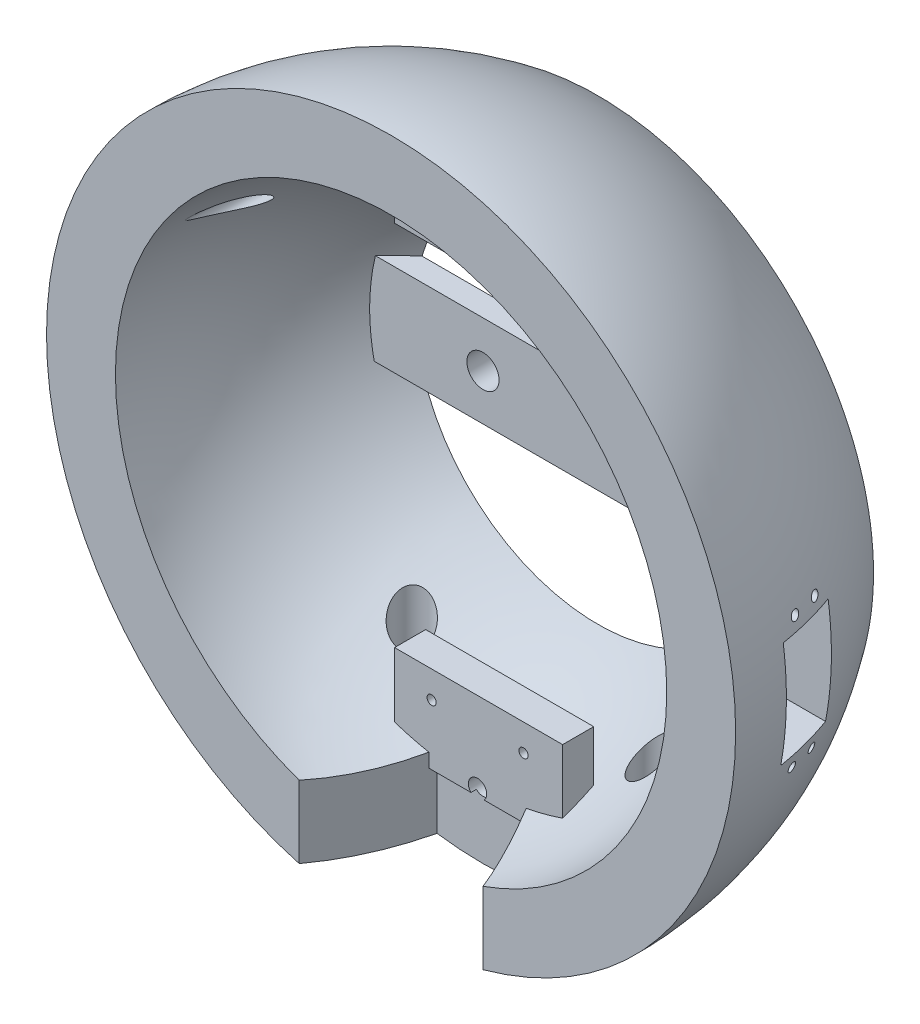
SolidWorks part; units mm, degrees
material "ABS"
ref_plane "Plano frontal" through (0, 0, 0) normal (0, 0, 1) x (1, 0, 0)
ref_plane "Plano superior" through (0, 0, 0) normal (0, 1, 0) x (1, 0, 0)
ref_plane "Plano direito" through (0, 0, 0) normal (1, 0, 0) x (0, 0, -1)
sketch "Esboço1" plane through (0, 0, 0) normal (0, 0, 1) x (1, 0, 0)
  line L0 (-60, 0) -> (-75, 0)
  line L1 (-60, 0) -> (-211.1575, 0) construction
  line L2 (75, 0) -> (60, 0)
  arc A0 (60, 0) -> (-60, 0) centre (0, 0) ccw
  arc A1 (75, 0) -> (-75, 0) centre (0, 0) ccw
  dimension "D1" = 120
  dimension "D2" = 150
revolve "Revolução1" add sketch "Esboço1" angle 180 about L1
ref_axis "Eixo1" through (0, 0, -79.24) along (0, 0, 1)
sketch "Esboço5" plane through (0, 0, 0) normal (0, 1, 0) x (1, 0, 0)
  line L0 (-75, 0) -> (75, 0) construction
  circle A0 centre (26, 30.5) radius 3.95
  circle A1 centre (-26, 30.5) radius 3.95
  dimension "D1" = 7.9
  dimension "D2" = 7.9
  dimension "D6" = 26
  dimension "D3" = 26
  dimension "D4" = 30.5
  dimension "D5" = 30.5
extrude "Corte-extrusão2" cut sketch "Esboço5" against normal through all
sketch "Esboço6" plane through (0, 0, 0) normal (0, 0, 1) x (1, 0, 0)
  circle A0 centre (-7.5, 0) radius 3.95
  circle A1 centre (7.5, 0) radius 3.95
  circle A2 centre (0, 0) radius 75 construction
  dimension "D1" = 7.9
  dimension "D2" = 7.9
  dimension "D4" = 7.5
  dimension "D3" = 15
  dimension "D5" = 0
extrude "Corte-extrusão4" cut sketch "Esboço6" against normal through all
sketch "Esboço7" plane through (0, 0, 0) normal (1, 0, 0) x (0, 0, -1)
  line L0 (0, 75) -> (0, -75) construction
  line L1 (12, 10) -> (25.2, 10)
  line L2 (12, 10) -> (12, -13.4)
  line L3 (12, -13.4) -> (25.2, -13.4)
  line L4 (25.2, 10) -> (25.2, -13.4)
  dimension "D1" = 23.4
  dimension "D2" = 13.2
  dimension "D3" = 12
  dimension "D4" = 10
extrude "Corte-extrusão5" cut sketch "Esboço7" along normal through all
sketch "Esboço8" plane through (0, 0, 0) normal (0, 1, 0) x (1, 0, 0)
  line L0 (0, 0) -> (0, 20) construction
  line L2 (0, 20) -> (10, 20)
  line L3 (0, 20) -> (-10, 20)
  line L4 (0, 0) -> (20, 0)
  line L5 (-75, 0) -> (75, 0) construction
  line L8 (0, 0) -> (-20, 0)
  line L9 (-10, 20) -> (-20, 0)
  line L10 (10, 20) -> (20, 0)
  dimension "D1" = 20
  dimension "D2" = 10
  dimension "D3" = 10
  dimension "D4" = 20
  dimension "D5" = 20
extrude "Corte-extrusão6" cut sketch "Esboço8" against normal through all
sketch "Esboço9" plane through (0, 0, 0) normal (1, 0, 0) x (0, 0, -1)
  line L0 (12, 10) -> (25.2, 10) construction
  circle A0 centre (15.7, 12.8) radius 1
  circle A1 centre (21.5, 12.8) radius 1
  circle A2 centre (15.7, -16.2) radius 1
  circle A3 centre (21.5, -16.2) radius 1
  point P4 (18.6, 10)
  dimension "D1" = 2
  dimension "D2" = 2
  dimension "D6" = 2
  dimension "D7" = 2
  dimension "D3" = 5.8
  dimension "D4" = 2.9
  dimension "D5" = 0
  dimension "D8" = 5.8
  dimension "D9" = 2.8
  dimension "D10" = 2.8
  dimension "D11" = 2.8
extrude "Corte-extrusão7" cut sketch "Esboço9" along normal blind 99
sketch "Esboço10" plane through (0, 0, 0) normal (0, 1, 0) x (1, 0, 0)
  line L0 (-18.0677, 18.8206) -> (18.517, 18.8206)
  line L1 (18.517, 18.8206) -> (18.517, 25.5896)
  line L2 (-18.0677, 25.5896) -> (-18.0677, 18.8206)
  line L3 (18.517, 25.5896) -> (-18.0677, 25.5896)
extrude "Ressalto-extrusão2" add sketch "Esboço10" against normal blind 59 and the other way blind 60
sketch "Esboço11" plane through (0, 0, 0) normal (0, 0, 1) x (1, 0, 0)
  line L1 (-20, 40) -> (20, 40)
  line L2 (-20, 40) -> (-20, -40)
  line L3 (-20, -40) -> (20, -40)
  line L4 (20, 40) -> (20, -40)
  arc A0 (18.517, 53.8786) -> (-18.0677, 54.031) centre (0, 0) ccw construction
  arc A1 (10.5897, -55.979) -> (18.517, -53.8786) centre (0, 0) ccw construction
  dimension "D1" = 20
  dimension "D2" = 20
  dimension "D3" = 40
  dimension "D4" = 40
extrude "Corte-extrusão8" cut sketch "Esboço11" against normal blind 28
sketch "Esboço12" plane through (0, 0, 0) normal (0, 0, 1) x (1, 0, 0)
  line L0 (0, -72.2842) -> (0, 75) construction
  line L1 (0, -46.64) -> (0, 46.64) construction
  line L2 (-67.6, 0) -> (67.6, 0) construction
  line L6 (0.2246, 40) -> (0, -40.0013) construction
  line L7 (-18.0677, 40) -> (18.517, 40) construction
  line L8 (10, 45.8574) -> (10, -45.8574) construction
  line L9 (10, -45.8574) -> (10, 45.8574) construction
  circle A0 centre (0, 0) radius 75 construction
  circle A1 centre (-10, -45.8574) radius 1
  circle A2 centre (10, -45.8574) radius 1
  arc A3 (10.5897, -55.979) -> (18.517, -53.8786) centre (0, 0) ccw construction
  arc A4 (-7.3761, -57.9943) -> (10.1239, -57.5783) centre (0, 0) ccw construction
  circle A5 centre (10, 45.8574) radius 1
  circle A6 centre (-10, 45.8574) radius 1
  arc A7 (-10, -71.5891) -> (10, -71.5891) centre (0, 0) ccw construction
  dimension "D1" = 2
  dimension "D2" = 2
  dimension "D4" = 10
  dimension "D5" = 10
  dimension "D6" = 91.7147
ref_plane "Plane2" through (0, 0, 0) normal (0, 0, 1) x (1, 0, 0)
sketch "Sketch5" plane through (0, 0, -45) normal (0, 0, 1) x (1, 0, 0)
  line L1 (-74.9651, 76.5351) -> (76.9276, 76.5351)
  line L2 (-74.9651, 76.5351) -> (-74.9651, -79.2825)
  line L3 (-74.9651, -79.2825) -> (76.9276, -79.2825)
  line L4 (76.9276, 76.5351) -> (76.9276, -79.2825)
extrude "Cut-Extrude2" cut sketch "Sketch5" against normal blind 45
ref_plane "Plane5" through (0, 0, -45) normal (0, 0, -1) x (-1, 0, 0)
sketch "Sketch8" plane through (0, 0, -45) normal (0, 0, -1) x (-1, 0, 0)
  line L0 (0, 0) -> (0, -60) construction
  circle A0 centre (0, 0) radius 60 construction
  circle A1 centre (0, -57.602) radius 2
  circle A2 centre (-49.8848, 28.801) radius 2
  circle A3 centre (49.8848, 28.801) radius 2
  point P14 (0, 0)
  dimension "D1" = 4
  dimension "D2" = 57.602
extrude "Cut-Extrude3" cut sketch "Sketch8" against normal blind 45
ref_plane "Plane6" through (64, 0, 0) normal (1, 0, 0) x (0, 0, -1)
sketch "Sketch9" plane through (64, 0, 0) normal (1, 0, 0) x (0, 0, -1)
  line L0 (-8, -10) -> (0, 10.1062) construction
  line L1 (0, 81.0063) -> (0, -81.0063) construction
  line L2 (-8, 10) -> (0, -10) construction
  circle A0 centre (-4, 0.0531) radius 1
  dimension "D1" = 2
extrude "Cut-Extrude4" cut sketch "Sketch9" against normal blind 165 rebuild error yes
sketch "Sketch10" plane through (0, 0, -45) normal (0, 0, -1) x (-1, 0, 0)
  line L1 (-47.8835, 10.5972) -> (51.8084, 10.5972)
  line L2 (-47.8835, 10.5972) -> (-47.8835, -9.4197)
  line L3 (-47.8835, -9.4197) -> (51.8084, -9.4197)
  line L4 (51.8084, 10.5972) -> (51.8084, -9.4197)
extrude "Boss-Extrude2" add sketch "Sketch10" against normal blind 5 separate body
sketch "Sketch11" plane through (0, 0, -45) normal (0, 0, 1) x (1, 0, 0)
  line L0 (47.8835, 10.5972) -> (-51.8084, -9.4197) construction
  line L1 (-51.8084, -9.4197) -> (-51.8084, 10.5972) construction
  line L2 (-51.8084, 10.5972) -> (47.8835, -9.4197) construction
  line L3 (47.8835, -9.4197) -> (47.8835, 0.5887) construction
  line L4 (47.8835, 10.5972) -> (47.8835, -9.4197) construction
  line L5 (47.8835, 0.5887) -> (-51.8084, 0.5887) construction
  circle A0 centre (20, 0.5887) radius 3.5
  circle A1 centre (-20, 0.5887) radius 3.5
  dimension "D1" = 7
  dimension "D2" = 7
  dimension "D3" = 20
  dimension "D4" = 20
extrude "Cut-Extrude5" cut sketch "Sketch11" along normal blind 44
extrude "Cut-Extrude6" cut sketch "Esboço12" against normal blind 32
